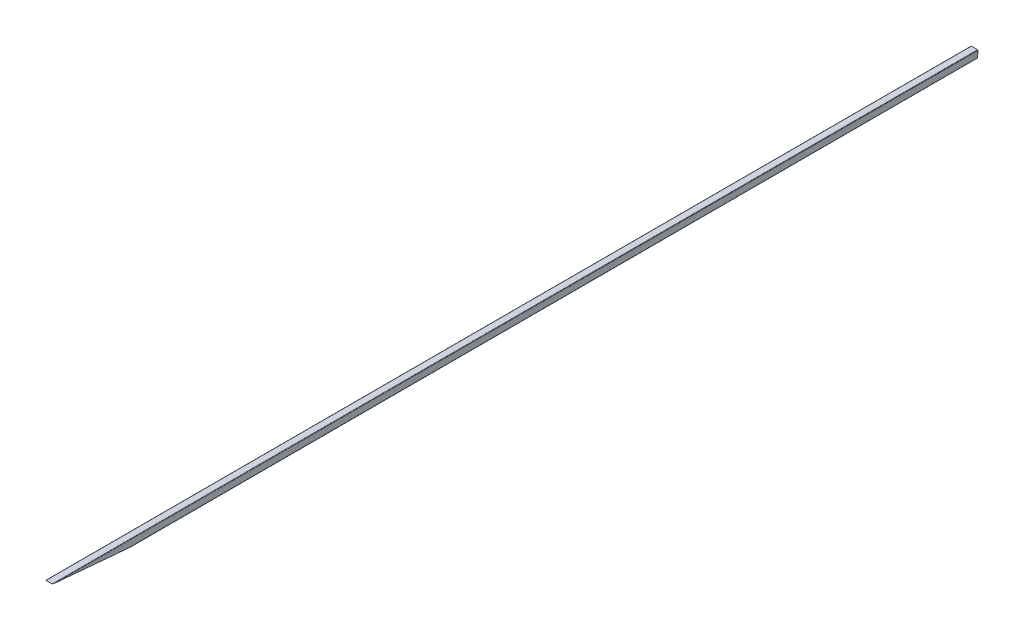
SolidWorks part; units mm, degrees
material "ASTM A500 Grade B"
ref_plane "Front Plane" through (0, 0, 0) normal (0, 0, 1) x (1, 0, 0)
ref_plane "Top Plane" through (0, 0, 0) normal (0, 1, 0) x (1, 0, 0)
ref_plane "Right Plane" through (0, 0, 0) normal (1, 0, 0) x (0, 0, -1)
sketch "Sketch1" plane through (0, 0, 0) normal (0, 0, 1) x (1, 0, 0)
  line L0 (5.3086, -2.7686) -> (32.7914, -2.7686)
  line L1 (2.54, 0) -> (35.56, 0)
  line L2 (0, -2.54) -> (0, -35.56)
  line L3 (2.54, -38.1) -> (35.56, -38.1)
  line L4 (38.1, -2.54) -> (38.1, -35.56)
  line L5 (35.3314, -5.3086) -> (35.3314, -32.7914)
  line L6 (5.3086, -35.3314) -> (32.7914, -35.3314)
  line L7 (2.7686, -5.3086) -> (2.7686, -32.7914)
  line L8 (0, 0) -> (0, -38.1) construction
  line L9 (0, -38.1) -> (38.1, -38.1) construction
  line L10 (38.1, 0) -> (38.1, -38.1) construction
  line L11 (2.7686, -2.7686) -> (2.7686, -35.3314) construction
  line L12 (2.7686, -35.3314) -> (35.3314, -35.3314) construction
  line L13 (35.3314, -2.7686) -> (35.3314, -35.3314) construction
  line L14 (2.7686, -2.7686) -> (35.3314, -2.7686) construction
  line L15 (0, 0) -> (38.1, 0) construction
  arc A0 (0, -35.56) -> (2.54, -38.1) centre (2.54, -35.56) ccw
  arc A1 (38.1, -35.56) -> (35.56, -38.1) centre (35.56, -35.56) cw
  arc A2 (2.7686, -32.7914) -> (5.3086, -35.3314) centre (5.3086, -32.7914) ccw
  arc A3 (32.7914, -35.3314) -> (35.3314, -32.7914) centre (32.7914, -32.7914) ccw
  arc A4 (35.3314, -5.3086) -> (32.7914, -2.7686) centre (32.7914, -5.3086) ccw
  arc A5 (38.1, -2.54) -> (35.56, 0) centre (35.56, -2.54) ccw
  arc A6 (0, -2.54) -> (2.54, 0) centre (2.54, -2.54) cw
  arc A7 (5.3086, -2.7686) -> (2.7686, -5.3086) centre (5.3086, -5.3086) ccw
  point P12 (0, -38.1)
  dimension "D4" = 2.54
  dimension "D3" = 2.7686
extrude "Boss-Extrude1" add sketch "Sketch1" along normal blind 5000
sketch "Sketch2" plane through (38.1, 0, 0) normal (1, 0, 0) x (0, 0, -1)
  line L0 (-5000, 0) -> (-4564.515, -38.1)
  line L1 (-5000, -38.1) -> (0, -38.1) construction
  line L2 (-5000, 0) -> (0, 0) construction
  line L3 (-4564.515, -38.1) -> (-5000, -38.1)
  line L4 (-5000, -38.1) -> (-5000, 0)
  dimension "D1" = 5
extrude "Cut-Extrude1" cut sketch "Sketch2" against normal through all
sketch "Sketch4" plane through (38.1, 0, 0) normal (1, 0, 0) x (0, 0, -1)
  line L0 (0, 0) -> (-3.3333, -38.1)
  line L1 (-4564.515, -38.1) -> (0, -38.1) construction
  line L2 (0, -35.56) -> (0, -2.54) construction
  line L3 (-3.3333, -38.1) -> (0, -38.1)
  line L4 (0, -38.1) -> (0, 0)
  dimension "D1" = 5
extrude "Cut-Extrude2" cut sketch "Sketch4" against normal through all
